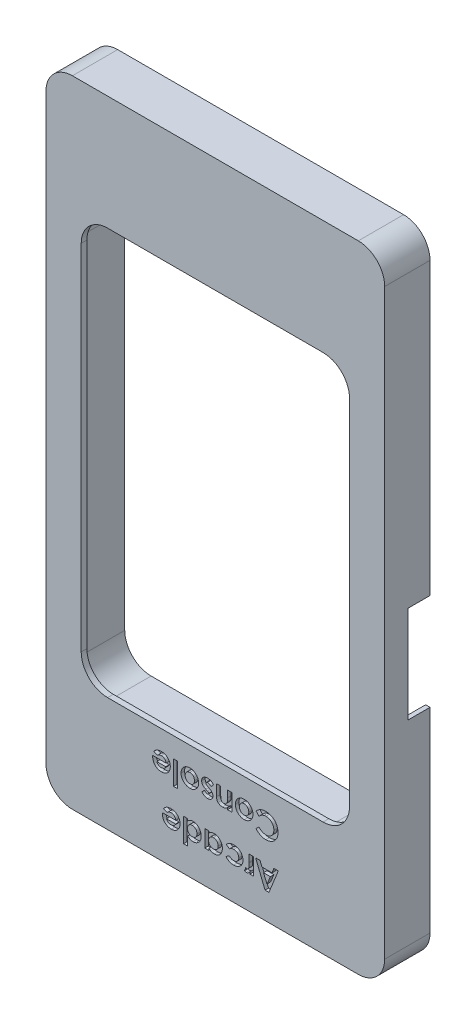
SolidWorks part; units mm, degrees
ref_plane "Ebene vorne" through (0, 0, 0) normal (1, 0, 0) x (0, 1, 0)
ref_plane "Ebene oben" through (0, 0, 0) normal (0, 0, 1) x (0, 1, 0)
ref_plane "Ebene rechts" through (0, 0, 0) normal (0, 1, 0) x (-1, 0, 0)
sketch "DiplayCase" plane through (0, 0, 0) normal (0, 0, 1) x (0, 1, 0)
  line L1 (-46.22, -30.5) -> (46.22, -30.5)
  line L2 (-46.22, -30.5) -> (-46.22, 30.5)
  line L3 (-46.22, 30.5) -> (46.22, 30.5)
  line L4 (46.22, -30.5) -> (46.22, 30.5)
  line L5 (-46.22, -30.5) -> (46.22, 30.5) construction
  line L6 (-46.22, 30.5) -> (46.22, -30.5) construction
  line L7 (-72.22, -38.5) -> (72.22, -38.5)
  line L8 (-72.22, -38.5) -> (-72.22, 38.5)
  line L9 (-72.22, 38.5) -> (72.22, 38.5)
  line L10 (72.22, -38.5) -> (72.22, 38.5)
  line L11 (-72.22, -38.5) -> (72.22, 38.5) construction
  line L12 (-72.22, 38.5) -> (72.22, -38.5) construction
  point P0 (0, 0)
  point P6 (0, 0)
  dimension "D1" = 61
  dimension "D2" = 92.44
  dimension "D3" = 8
  dimension "D4" = 26
extrude "UpperCase" add sketch "DiplayCase" along normal blind 10.3
fillet "Verrundung1" radius 6 4 edges at (30.5, 46.22, 5.15) (-30.5, 46.22, 5.15) (30.5, -46.22, 5.15) (-30.5, -46.22, 5.15)
sketch "Skizze2" plane through (0, 0, 0) normal (0, 0, -1) x (1, 0, 0)
  line L1 (-30.9, -47.32) -> (30.9, -47.32)
  line L2 (-30.9, -47.32) -> (-30.9, 47.32)
  line L3 (-30.9, 47.32) -> (30.9, 47.32)
  line L4 (30.9, -47.32) -> (30.9, 47.32)
  line L5 (-30.9, -47.32) -> (30.9, 47.32) construction
  line L6 (-30.9, 47.32) -> (30.9, -47.32) construction
  point P0 (0, 0)
  dimension "D1" = 61.8
  dimension "D2" = 94.64
extrude "Schnitt-Linear austragen1" cut sketch "Skizze2" against normal blind 9
fillet "Verrundung2" radius 6 4 edges at (38.5, -72.22, 5.15) (-38.5, -72.22, 5.15) (38.5, 72.22, 5.15) (-38.5, 72.22, 5.15)
fillet "Verrundung3" radius 6 4 edges at (-30.9, 47.32, 4.5) (30.9, 47.32, 4.5) (30.9, -47.32, 4.5) (-30.9, -47.32, 4.5)
shell "Wandung2" thickness 1 removed face at (0, 0, 0)
sketch "Skizze8" plane through (0, 0, 10.3) normal (0, 0, 1) x (0, -1, 0)
  line L0 (46.22, 0) -> (72.22, 0) construction
  line L1 (46.22, -24.5) -> (46.22, 24.5) construction
  line L2 (72.22, -32.5) -> (72.22, 32.5) construction
  line L3 (60.9348, 18.5) -> (60.9348, -18.5) construction
  text T0 "Arcade \r\nConsole" font "Century Gothic" height in points 20
  point P10 (60.9348, 0)
extrude "Text_ArcadeConsole" cut sketch "Skizze8" against normal blind 0.8
sketch "Skizze11" plane through (0, 47.32, 0) normal (0, -1, 0) x (1, 0, 0)
  line L1 (-10.85, -4.17) -> (10.85, -4.17)
  line L2 (-10.85, -4.17) -> (-10.85, 4.17)
  line L3 (-10.85, 4.17) -> (10.85, 4.17)
  line L4 (10.85, -4.17) -> (10.85, 4.17)
  line L5 (-10.85, -4.17) -> (10.85, 4.17) construction
  line L6 (-10.85, 4.17) -> (10.85, -4.17) construction
  point P0 (0, 0)
  dimension "D1" = 21.7
  dimension "D2" = 8.34
extrude "Hole_DisplayCables" cut sketch "Skizze11" against normal blind 1
sketch "Skizze12" plane through (0, 0, 9.3) normal (0, 0, -1) x (1, 0, 0)
  line L1 (-31.5, -66) -> (31.5, -66) construction
  line L2 (-31.5, -66) -> (-31.5, 66) construction
  line L3 (-31.5, 66) -> (31.5, 66) construction
  line L4 (31.5, -66) -> (31.5, 66) construction
  line L5 (-31.5, -66) -> (31.5, 66) construction
  line L6 (-31.5, 66) -> (31.5, -66) construction
  circle A2 centre (34, 68) radius 2.5
  circle A3 centre (34, 68) radius 1.25
  circle A4 centre (-34, 68) radius 2.5
  circle A5 centre (-34, 68) radius 1.25
  circle A6 centre (34, -68) radius 2.5
  circle A7 centre (34, -68) radius 1.25
  circle A8 centre (-34, -68) radius 2.5
  circle A9 centre (-34, -68) radius 1.25
  point P0 (0, 0)
  dimension "D3" = 5
  dimension "D4" = 2.5
  dimension "D6" = 2.5
  dimension "D7" = 5
  dimension "D8" = 2.5
  dimension "D11" = 5
  dimension "D12" = 2.5
  dimension "D15" = 5
  dimension "D16" = 2.5
  dimension "D1" = 63
  dimension "D2" = 132
  dimension "D5" = 2
  dimension "D9" = 2.5
  dimension "D10" = 2
  dimension "D13" = 2.5
  dimension "D14" = 2
extrude "Aufsatz-Linear austragen4" add sketch "Skizze12" along normal blind 4 contours A6 | A7 | A4 | A5 | A3 | A2 | A8 | A9
sketch "Skizze16" plane through (38.5, 0, 0) normal (1, 0, 0) x (0, 1, 0)
  line L0 (-66.22, 0) -> (66.22, 0) construction
  line L2 (0.22, 0) -> (-21.78, 0)
  line L3 (0.22, 0) -> (0.22, 5)
  line L4 (0.22, 5) -> (-21.78, 5)
  line L5 (-21.78, 0) -> (-21.78, 5)
  dimension "D1" = 66
  dimension "D2" = 22
  dimension "D3" = 5
extrude "Schnitt-Linear austragen3" cut sketch "Skizze16" against normal blind 11
sketch "Skizze18" plane through (-38.5, 0, 0) normal (-1, 0, 0) x (0, -1, 0)
  line L0 (-66.22, 5.15) -> (-35.1656, 5.15) construction
  line L1 (-66.22, 10.3) -> (-66.22, 0) construction
  line L2 (-63.72, 5.15) -> (-53.78, 5.15) construction
  line L3 (-63.72, 7.28) -> (-53.78, 7.28)
  line L4 (-63.72, 3.02) -> (-53.78, 3.02)
  arc A0 (-63.72, 7.28) -> (-63.72, 3.02) centre (-63.72, 5.15) ccw
  arc A1 (-53.78, 3.02) -> (-53.78, 7.28) centre (-53.78, 5.15) ccw
  point P6 (-58.75, 5.15)
  dimension "D1" = 9.94
  dimension "D2" = 4.26
  dimension "D3" = 2.5
extrude "Schnitt-Linear austragen4" cut sketch "Skizze18" against normal blind 1
